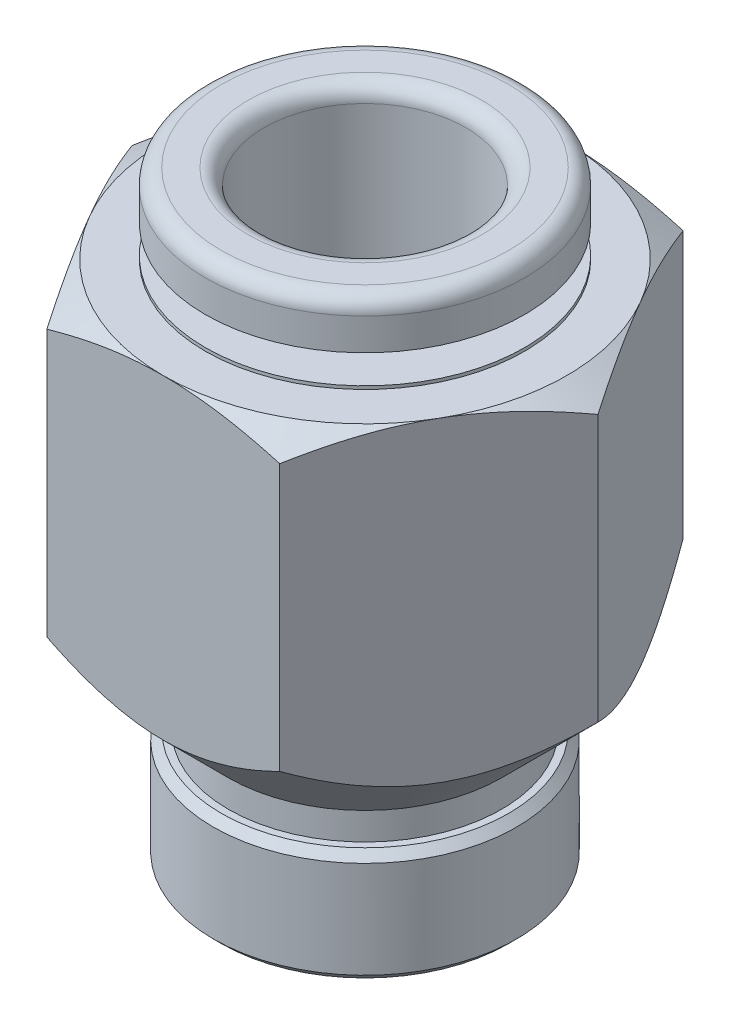
SolidWorks part; units mm, degrees
ref_plane "Front" through (0, 0, 0) normal (0, 0, 1) x (1, 0, 0)
ref_plane "Top" through (0, 0, 0) normal (0, 1, 0) x (1, 0, 0)
ref_plane "Right" through (0, 0, 0) normal (1, 0, 0) x (0, 0, -1)
ref_plane "URelease_Height" through (0, -2.4, 0) normal (0, 1, 0) x (-1, 0, 0)
ref_plane "LRelease_Height" [suppressed] through (0, -24.6, 0) normal (0, 1, 0) x (-1, 0, 0)
ref_plane "UBody_Height" through (0, -2.5, 0) normal (0, 1, 0) x (-1, 0, 0)
ref_plane "LBody_Height" [suppressed] through (0, -13.8, 0) normal (0, 1, 0) x (-1, 0, 0)
ref_plane "Nut_Thickness" through (0, -14.49, 0) normal (0, 1, 0) x (-1, 0, 0)
ref_plane "Nut_Offset" [suppressed] through (0, -14.5, 0) normal (0, 1, 0) x (-1, 0, 0)
ref_plane "L-Total_Height" through (0, -18.9, 0) normal (0, 1, 0) x (-1, 0, 0)
ref_plane "Mirror_Plane-MidPlane" [suppressed] through (0, -16.25, 0) normal (0, 1, 0) x (-1, 0, 0)
ref_plane "M-UTube_Depth" through (0, -13.3, 0) normal (0, 1, 0) x (-1, 0, 0)
ref_plane "M-LTube_Depth" [suppressed] through (0, -14.3, 0) normal (0, 1, 0) x (-1, 0, 0)
sketch "URelease_Sketch" plane through (0, 0, 0) normal (0, 0, 1) x (1, 0, 0)
  line L0 (0, 0) -> (0, -31.0889) construction
  line L1 (0, 0) -> (-4.525, 0)
  line L2 (-5.025, -0.5) -> (-5.025, -1.5)
  line L3 (-5.025, -1.5) -> (-3.575, -1.5)
  line L4 (-3.575, -1.5) -> (-3.575, -2.4)
  line L5 (-3.575, -2.4) -> (0, -2.4)
  line L7 (9.9398, -2.4) -> (-9.9398, -2.4) construction
  line L8 (0, 0) -> (0, -2.4)
  arc A0 (-5.025, -0.5) -> (-4.525, 0) centre (-4.525, -0.5) cw
  point P12 (-5.025, 0)
  dimension "Radius" = 0.5
  dimension "Outer_Dia" = 10.05
  dimension "Tube_Dia" = 7.15
  dimension "Thickness" = 1.5
revolve "URelease" add sketch "URelease_Sketch" angle 360 about L0
sketch "UBody_Sketch" plane through (0, -2.4, 0) normal (0, 1, 0) x (-1, 0, 0)
  circle A0 centre (0, 0) radius 5.025
  dimension "Dia" = 10.05
extrude "UBody" add sketch "UBody_Sketch" against normal up to surface (0.1 mm away) up to plane "UBody_Height"
sketch "Nut_Sketch" plane through (0, -2.5, 0) normal (0, 1, 0) x (-1, 0, 0)
  line L1 (-3.6662, -6.35) -> (3.6662, -6.35)
  line L2 (3.6662, -6.35) -> (7.3323, 0)
  line L3 (7.3323, 0) -> (3.6662, 6.35)
  line L4 (3.6662, 6.35) -> (-3.6662, 6.35)
  line L5 (-3.6662, 6.35) -> (-7.3323, 0)
  line L6 (-7.3323, 0) -> (-3.6662, -6.35)
  circle A0 centre (0, 0) radius 6.35 construction
  dimension "Hex" = 12.7
extrude "Nut" add sketch "Nut_Sketch" against normal up to surface (11.99 mm away) up to plane "Nut_Thickness"
sketch "Nut_Chamfer_Sketch" plane through (0, 0, 0) normal (1, 0, 0) x (0, 0, -1)
  line L0 (-6.35, -8.495) -> (-8.8214, -8.495) construction
  line L1 (-6.35, -14.49) -> (-6.35, -2.5) construction
  line L2 (-6.35, -2.5) -> (0, -2.5) construction
  line L3 (-6.35, -2.5) -> (-9.35, -2.5)
  line L4 (-6.35, -2.5) -> (-9.35, -4.2321)
  line L5 (-9.35, -4.2321) -> (-9.35, -2.5)
  line L6 (0, 0) -> (0, -15.6305) construction
  line L8 (-9.35, -12.7579) -> (-9.35, -14.49)
  line L9 (-6.35, -14.49) -> (-9.35, -12.7579)
  line L10 (-6.35, -14.49) -> (-9.35, -14.49)
  dimension "Angle" = 30
  dimension "Dist" = 3
revolve "Nut_Chamfer" cut sketch "Nut_Chamfer_Sketch" angle 360 about L6
sketch "Offset_Sketch" plane through (0, -14.49, 0) normal (0, 1, 0) x (-1, 0, 0)
  circle A0 centre (0, 0) radius 3.6
  dimension "Dia" = 7.2
extrude "Offset" [suppressed] add sketch "Offset_Sketch" along normal up to surface (1.3 mm away)
sketch "Threads_Sketch" plane through (0, 0, 0) normal (0, 0, 1) x (1, 0, 0)
  line L0 (0, 0) -> (0, -24.1616) construction
  line L1 (-4.7715, -15.35) -> (-4.3, -15.35)
  line L2 (0, -14.49) -> (-4.3, -14.49)
  line L3 (-4.7715, -15.35) -> (-4.7715, -18.9)
  line L4 (-4.7715, -18.9) -> (0, -18.9)
  line L5 (0, -18.9) -> (0, -14.49)
  line L6 (-4.3, -15.35) -> (-4.3, -14.49)
  line L7 (10.7464, -18.9) -> (-10.7464, -18.9) construction
  line L8 (9.2936, -14.49) -> (-9.2936, -14.49) construction
  point P13 (-4.7715, -14.93)
  dimension "D1" = 8.6
  dimension "D2" = 3.55
  dimension "Angle" = 90
  dimension "a" = 3.97
  dimension "d" = 9.543
revolve "Threads" add sketch "Threads_Sketch" angle 360 about L0
chamfer "Thread_Chamfer" distance 0.25 angle 45 2 edges at (0, -18.9, 4.7715) (0, -15.35, 4.7715)
sketch "MBody-Half_Sketch" [suppressed] plane through (0, -13.8, 0) normal (0, 1, 0) x (-1, 0, 0)
  circle A0 centre (0, 0) radius 3.35
  dimension "Dia" = 14
extrude "MBody-Half" [suppressed] add sketch "MBody-Half_Sketch" against normal up to surface (2.45 mm away)
chamfer "UTube_Chamfer" [suppressed] distance 0.5 angle 20
sketch "MBody_Sketch" [suppressed] plane through (0, -14.9, 0) normal (0, 1, 0) x (-1, 0, 0)
  circle A0 centre (0, 0) radius 5
  dimension "Dia" = 8
extrude "MBody" [suppressed] add sketch "MBody_Sketch" against normal up to surface (4.8 mm away)
sketch "LBody_Sketch" [suppressed] plane through (0, -13.8, 0) normal (0, 1, 0) x (-1, 0, 0)
  circle A0 centre (0, 0) radius 5.2
  dimension "D1" = 8.2
extrude "LBody" [suppressed] add sketch "LBody_Sketch" against normal up to surface (10.8 mm away)
sketch "LRelease_Sketch" [suppressed] plane through (0, 0, 0) normal (0, 0, 1) x (1, 0, 0)
  line L0 (0, 0) -> (0, -33.5328) construction
  line L1 (0, -13.8) -> (0, -3) construction
  line L2 (0, -24.6) -> (-3.4, -24.6)
  line L3 (-3.4, -24.6) -> (-3.4, -26.1)
  line L4 (-3.4, -26.1) -> (-4.85, -26.1)
  line L5 (-4.85, -26.1) -> (-4.85, -27.1)
  line L6 (-4.35, -27.6) -> (0, -27.6)
  line L7 (0, -27.6) -> (0, -24.6)
  line L9 (7.072, -24.6) -> (-7.072, -24.6) construction
  line L10 (10.7464, -27.6) -> (-10.7464, -27.6) construction
  arc A0 (-4.35, -27.6) -> (-4.85, -27.1) centre (-4.35, -27.1) cw
  point P17 (-4.85, -27.6)
  dimension "Radius" = 0.5
  dimension "Tube_Dia" = 5
  dimension "Outside_Dia" = 9.5
  dimension "Thickness" = 1.5
revolve "LRelease" [suppressed] add sketch "LRelease_Sketch" angle 360 about L0
sketch "UTube_Sketch" plane through (0, 0, 0) normal (0, 1, 0) x (1, 0, 0)
  circle A0 centre (0, 0) radius 3.175
  dimension "Tube_Dia" = 6.35
extrude "UTube" cut sketch "UTube_Sketch" against normal up to surface (13.3 mm away) up to plane "M-UTube_Depth"
fillet "UTube_Radius" radius 0.5 1 edges at (0, 0, 3.175)
sketch "LTube_Sketch" [suppressed] plane through (0, -27.6, 0) normal (0, 1, 0) x (-1, 0, 0)
  circle A0 centre (0, 0) radius 3
  dimension "Dia" = 1
extrude "LTube" [suppressed] cut sketch "LTube_Sketch" along normal up to surface (13.3 mm away)
fillet "LTube_Radius" [suppressed] radius 0.5
mirror "Mirror_LBody" [suppressed] of bodies 107
chamfer "Tube_Chamfer" [suppressed] distance 0.15 angle 20
sketch "Port_Sketch" plane through (0, 0, 0) normal (0, 1, 0) x (1, 0, 0)
  circle A0 centre (0, 0) radius 1.9844
  dimension "Dia" = 3.9688
extrude "Port" cut sketch "Port_Sketch" against normal through all
sketch "Connecting Point" plane through (0, 0, 0) normal (0, 0, 1) x (1, 0, 0)
  line L1 (7.072, 0) -> (-7.072, 0) construction
  point P0 (0, -14.1)
  dimension "A" = 14.1
sketch "Sketch1" plane through (0, 0, 0) normal (0, 0, 1) x (1, 0, 0)
  line L0 (-4.3, -14.49) -> (-7.3323, -11.4577)
  line L1 (-7.3323, -13.9228) -> (-7.3323, -3.0672) construction
  line L2 (-7.3323, -11.4577) -> (-7.3323, -14.49)
  line L3 (-7.3323, -14.49) -> (-4.3, -14.49)
  line L4 (0, -18.9) -> (0, -2.5) construction
  line L5 (-4.5215, -18.9) -> (4.5215, -18.9) construction
  spline S0 degree 3 poles (-3.6662, -3.0672) (-3.0694, -2.8949) (-2.4589, -2.7506) (-1.2356, -2.5533) (-0.6201, -2.5) (0, -2.5) knots 0 0 0 0 0.5 0.5 1 1 1 1 construction
  dimension "D1" = 45
revolve "Cut-Revolve2" cut sketch "Sketch1" angle 360 about L4
